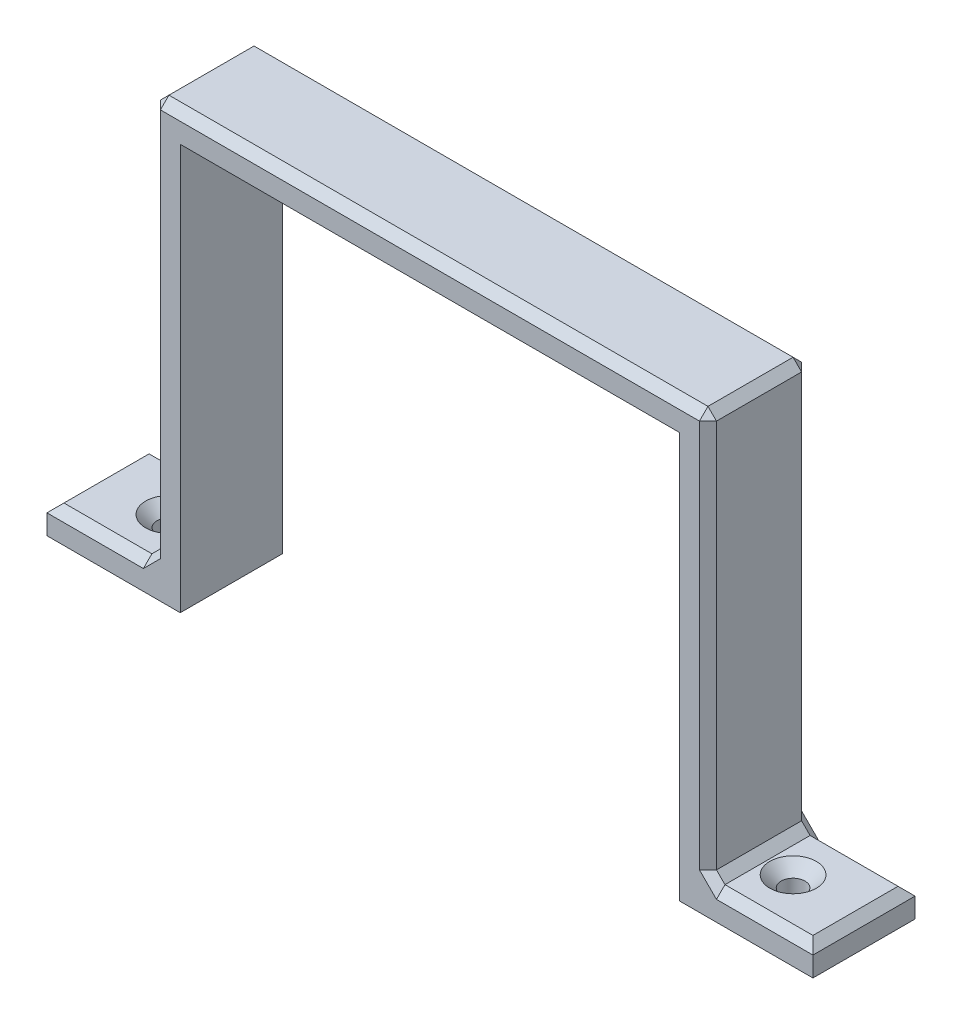
SolidWorks part; units mm, degrees
ref_plane "Front Plane" through (0, 0, 0) normal (0, 0, 1) x (1, 0, 0)
ref_plane "Top Plane" through (0, 0, 0) normal (0, 1, 0) x (1, 0, 0)
ref_plane "Right Plane" through (0, 0, 0) normal (1, 0, 0) x (0, 0, -1)
sketch "Sketch1" plane through (0, 0, 0) normal (0, 0, 1) x (1, 0, 0)
  line L0 (0, 48.7073) -> (0, -14.6895) construction
  line L1 (44, -27.85) -> (44, 43.65)
  line L2 (56.75, -27.85) -> (51.75, -27.85) construction
  line L3 (44, 43.65) -> (-44, 43.65)
  line L4 (-49, 48.65) -> (49, 48.65)
  line L5 (49, 48.65) -> (49, -22.85)
  line L6 (49, -22.85) -> (67.5, -22.85)
  line L7 (67.5, -22.85) -> (67.5, -27.85)
  line L8 (67.5, -27.85) -> (67.5, -43.45) construction
  line L9 (67.5, -27.85) -> (44, -27.85)
  line L10 (49, -22.85) -> (49, -27.85) construction
  line L11 (0, 48.65) -> (0, 43.65) construction
  line L12 (-49, -22.85) -> (-49, -27.85) construction
  line L13 (-67.5, -27.85) -> (-44, -27.85)
  line L14 (-67.5, -22.85) -> (-67.5, -27.85)
  line L15 (-49, -22.85) -> (-67.5, -22.85)
  line L16 (-49, 48.65) -> (-49, -22.85)
  line L17 (-44, -27.85) -> (-44, 43.65)
  dimension "D1" = 71.5
  dimension "D2" = 44
  dimension "D3" = 5
  dimension "D4" = 5
  dimension "D5" = 5
extrude "Boss-Extrude1" add sketch "Sketch1" along normal mid plane 18
sketch "Sketch2" plane through (0, -27.85, 0) normal (0, -1, 0) x (1, 0, 0)
  line L0 (0, 8.47) -> (0, -7.1138) construction
  circle A0 centre (55, 0) radius 2.1
  circle A1 centre (-55, 0) radius 2.1
  dimension "D1" = 4.2
extrude "Cut-Extrude1" cut sketch "Sketch2" against normal mid plane 18
chamfer "Chamfer1" distance 2 angle 45 2 edges at (-52.9, -22.85, 0) (55, -22.85, -2.1)
chamfer "Chamfer2" distance 1.5 angle 45 16 edges at (49, 48.65, 0) (0, 48.65, 9) (-49, 48.65, 0) (0, 48.65, -9) (-49, 12.9, 9) (-49, 12.9, -9) (-49, -22.85, 0) (-58.25, -22.85, 9) (-67.5, -22.85, 0) (-58.25, -22.85, -9) (49, 12.9, 9) (49, 12.9, -9) (67.5, -22.85, 0) (58.25, -22.85, 9) (49, -22.85, 0) (58.25, -22.85, -9)
